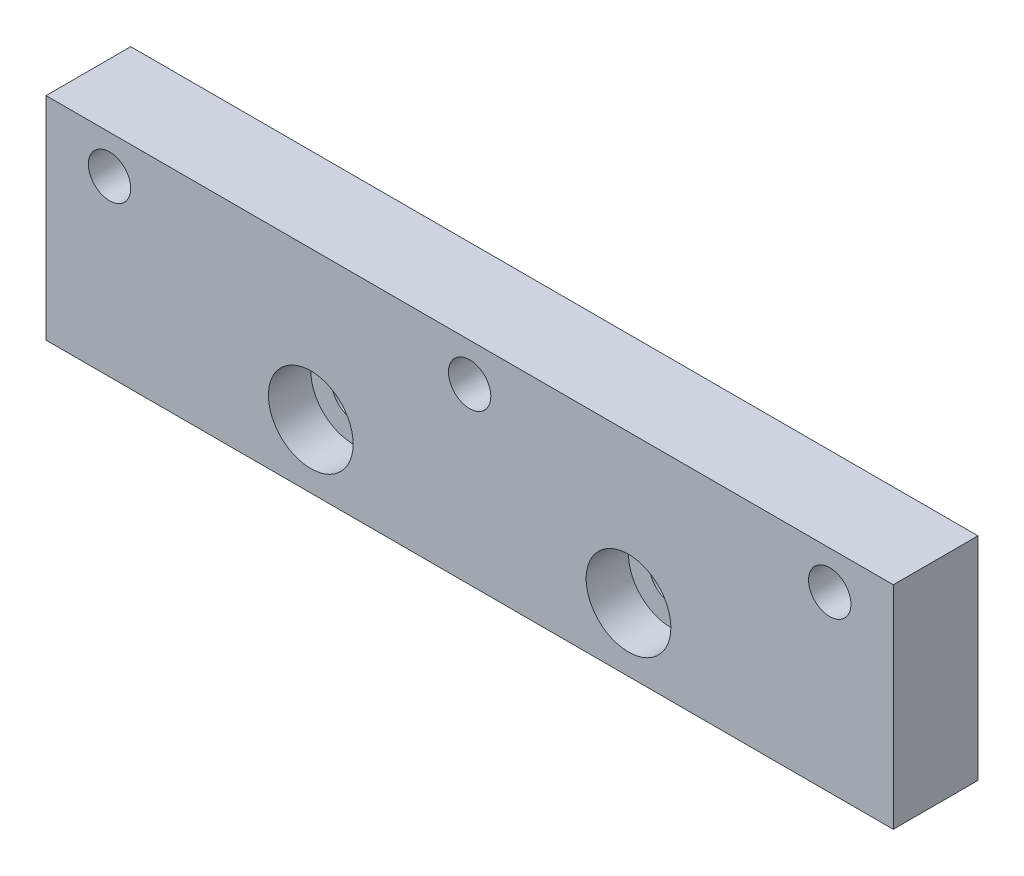
SolidWorks part; units mm, degrees
material "1060 Alloy"
ref_plane "Front Plane" through (0, 0, 0) normal (0, 0, 1) x (1, 0, 0)
ref_plane "Top Plane" through (0, 0, 0) normal (0, 1, 0) x (1, 0, 0)
ref_plane "Right Plane" through (0, 0, 0) normal (1, 0, 0) x (0, 0, -1)
sketch "Sketch2" plane through (0, 0, 0) normal (0, 0, 1) x (1, 0, 0)
  line L1 (-20, 5) -> (20, 5)
  line L2 (-20, 5) -> (-20, -5)
  line L3 (-20, -5) -> (20, -5)
  line L4 (20, 5) -> (20, -5)
  line L5 (-20, 5) -> (20, -5) construction
  line L6 (-20, -5) -> (20, 5) construction
  point P0 (0, 0)
  dimension "D1" = 10
  dimension "D2" = 40
extrude "Boss-Extrude1" add sketch "Sketch2" along normal blind 4
sketch "Sketch3" plane through (0, 0, 4) normal (0, 0, 1) x (1, 0, 0)
  line L1 (0, 5) -> (0, -5) construction
  line L2 (20, 5) -> (-20, 5) construction
  line L3 (-20, -5) -> (20, -5) construction
  line L4 (-7.5, -2) -> (7.5, -2) construction
  circle A0 centre (-17, 3.2) radius 1
  circle A1 centre (0, 3.2) radius 1
  circle A2 centre (17, 3.2) radius 1
  circle A3 centre (-7.5, -2) radius 1
  circle A4 centre (7.5, -2) radius 1
  point P19 (0, -2)
  dimension "D1" = 2
  dimension "D2" = 2
  dimension "D3" = 2
  dimension "D6" = 2
  dimension "D7" = 2
  dimension "D4" = 17
  dimension "D5" = 17
  dimension "D8" = 15
  dimension "D9" = 3
extrude "Cut-Extrude1" cut sketch "Sketch3" against normal through all
sketch "Sketch4" plane through (0, 0, 4) normal (0, 0, 1) x (1, 0, 0)
  circle A0 centre (-7.5, -2) radius 2
  circle A1 centre (7.5, -2) radius 2
  point P6 (-7.5, -2)
  point P7 (-7.5, -2)
  dimension "D1" = 4
  dimension "D2" = 4
extrude "Cut-Extrude2" cut sketch "Sketch4" against normal blind 2
